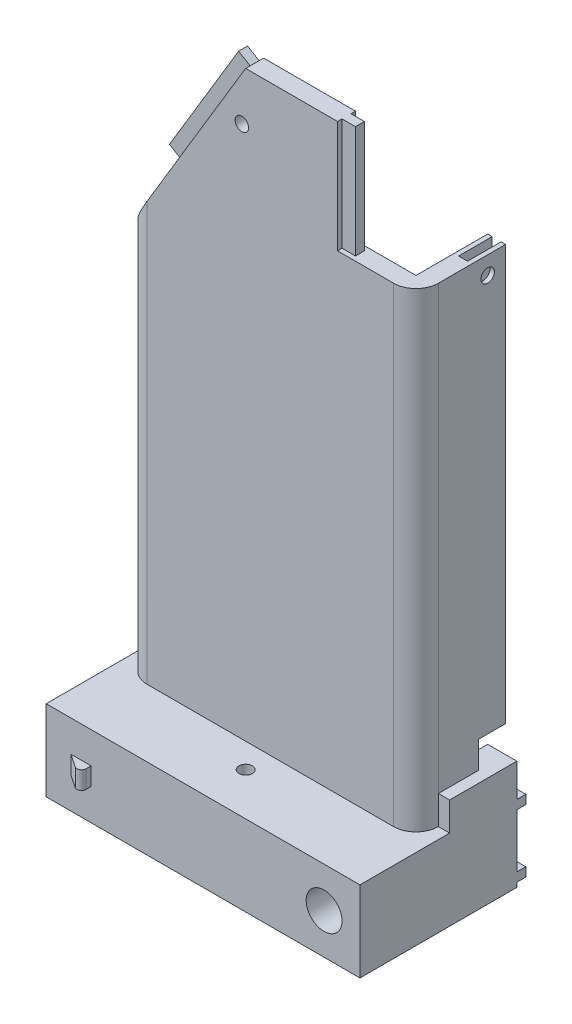
SolidWorks part; units mm, degrees
ref_plane "Front Plane" through (0, 0, 0) normal (0, 0, 1) x (1, 0, 0)
ref_plane "Top Plane" through (0, 0, 0) normal (0, 1, 0) x (1, 0, 0)
ref_plane "Right Plane" through (0, 0, 0) normal (1, 0, 0) x (0, 0, -1)
sketch "Sketch1" plane through (0, 0, 0) normal (0, 1, 0) x (1, 0, 0)
  line L1 (-32.5, -20) -> (32.5, -20)
  line L2 (-32.5, -20) -> (-32.5, 20)
  line L3 (-32.5, 20) -> (32.5, 20)
  line L4 (32.5, -20) -> (32.5, 20)
  line L5 (-32.5, -20) -> (32.5, 20) construction
  line L6 (-32.5, 20) -> (32.5, -20) construction
  point P0 (0, 0)
  dimension "D1" = 65
  dimension "D2" = 40
extrude "Boss-Extrude1" add sketch "Sketch1" along normal blind 130
shell "Shell1" thickness 4 removed face at (0, 0, 0) removed face at (0, 130, 0)
fillet "Fillet1" radius 5 4 edges at (32.5, 65, -20) (32.5, 65, 20) (-32.5, 65, -20) (-32.5, 65, 20)
sketch "Sketch2" plane through (0, 0, 0) normal (0, 0, 1) x (1, 0, 0)
  line L0 (-5.5, 130) -> (-32.5, 85)
  line L1 (28.5, 130) -> (-28.5, 130) construction
  line L2 (-32.5, 130) -> (-32.5, 0) construction
  line L3 (-32.5, 85) -> (-32.5, 130)
  line L4 (-32.5, 130) -> (-5.5, 130)
  dimension "D1" = 5.5
  dimension "D2" = 85
extrude "Cut-Extrude1" cut sketch "Sketch2" against normal through all both and the other way through all
sketch "Sketch3" plane through (0, 0, 0) normal (0, 0, 1) x (1, 0, 0)
  line L1 (32.5, 130) -> (15, 130)
  line L2 (32.5, 130) -> (32.5, 105)
  line L3 (32.5, 105) -> (15, 105)
  line L4 (15, 130) -> (15, 105)
  dimension "D1" = 25
  dimension "D2" = 17.5
extrude "Cut-Extrude2" cut sketch "Sketch3" against normal through all both and the other way through all
sketch "Sketch5" plane through (15, 0, 0) normal (1, 0, 0) x (0, 0, -1)
  line L0 (-18, 130) -> (-18, 105) construction
  line L1 (-16, 130) -> (-20, 130) construction
  line L2 (-16, 105) -> (-20, 105) construction
  line L4 (-19, 130) -> (-17, 130)
  line L5 (-19, 130) -> (-19, 105)
  line L6 (-19, 105) -> (-17, 105)
  line L7 (-17, 130) -> (-17, 105)
  dimension "D1" = 2
extrude "Boss-Extrude2" add sketch "Sketch5" along normal blind 3
mirror "Mirror1" about plane through (0, 0, 0) normal (0, 0, 1) of "Boss-Extrude2"
sketch "Sketch6" plane through (-61.3971, 36.8382, 0) normal (-0.8575, 0.5145, 0) x (0, 0, 1)
  line L0 (-18, 108.6444) -> (-18, 78.6444) construction
  line L1 (-20, 108.6444) -> (-16, 108.6444) construction
  line L3 (-19, 108.6444) -> (-17, 108.6444)
  line L4 (-19, 108.6444) -> (-19, 78.6444)
  line L5 (-19, 78.6444) -> (-17, 78.6444)
  line L6 (-17, 108.6444) -> (-17, 78.6444)
  dimension "D1" = 30
  dimension "D2" = 2
extrude "Boss-Extrude3" add sketch "Sketch6" along normal blind 3
mirror "Mirror2" about plane through (0, 0, 0) normal (0, 0, 1) of "Boss-Extrude3"
sketch "Sketch8" plane through (0, 0, 0) normal (0, 1, 0) x (1, 0, 0)
  line L1 (-35, -35) -> (35, -35)
  line L2 (-35, -35) -> (-35, 35)
  line L3 (-35, 35) -> (35, 35)
  line L4 (35, -35) -> (35, 35)
  line L5 (-35, -35) -> (35, 35) construction
  line L6 (-35, 35) -> (35, -35) construction
  point P0 (0, 0)
  dimension "D1" = 70
  dimension "D2" = 70
extrude "Boss-Extrude4" add sketch "Sketch8" against normal blind 18
sketch "Sketch10" plane through (-35, 0, 0) normal (-1, 0, 0) x (0, 0, 1)
  line L0 (-35, -9) -> (35, -9) construction
  line L1 (-30, -14) -> (30, -14)
  line L2 (-30, -14) -> (-30, -4)
  line L3 (-30, -4) -> (30, -4)
  line L4 (30, -14) -> (30, -4)
  line L5 (-30, -14) -> (30, -4) construction
  line L6 (-30, -4) -> (30, -14) construction
  line L7 (-35, -18) -> (-35, 0) construction
  line L8 (35, -18) -> (35, 0) construction
  line L9 (0, 0) -> (0, -18) construction
  line L10 (-35, -18) -> (35, -18) construction
  point P0 (0, -9)
  dimension "D1" = 60
  dimension "D2" = 10
extrude "Cut-Extrude4" cut sketch "Sketch10" against normal blind 45
sketch "Sketch23" plane through (0, 105, 0) normal (0, 1, 0) x (1, 0, 0)
  line L0 (0, 0) -> (32.5, 0) construction
  line L1 (29.5, 7.5) -> (31.5, 7.5)
  line L2 (29.5, 7.5) -> (29.5, -7.5)
  line L3 (29.5, -7.5) -> (31.5, -7.5)
  line L4 (31.5, 7.5) -> (31.5, -7.5)
  line L5 (32.5, 15) -> (32.5, -15) construction
  line L6 (28.5, 16) -> (28.5, -16) construction
  line L8 (30.5, 14.75) -> (30.5, -14.75) construction
  dimension "D1" = 2
  dimension "D2" = 15
extrude "Cut-Extrude10" cut sketch "Sketch23" against normal blind 10
sketch "Sketch24" plane through (32.5, 0, 0) normal (1, 0, 0) x (0, 0, -1)
  line L1 (15, 105) -> (-15, 105) construction
  circle A0 centre (-4, 101) radius 1.5
  point P2 (0, 105)
  dimension "D3" = 3
  dimension "D1" = 4
  dimension "D2" = 4
extrude "Cut-Extrude11" cut sketch "Sketch24" against normal blind 10 and the other way through all
mirror "Mirror4" about plane through (0, 0, 0) normal (0, 0, 1) of "Cut-Extrude11"
sketch "Sketch27" plane through (0, 0, 0) normal (0, 1, 0) x (1, 0, 0)
  line L0 (35, -35) -> (35, 35) construction
  line L1 (-35, 35) -> (35, 35)
  line L2 (-35, 35) -> (-35, 0)
  line L3 (-35, 0) -> (35, 0)
  line L4 (35, 35) -> (35, 0)
extrude "Cut-Extrude12" cut sketch "Sketch27" against normal through all both and the other way through all
sketch "Sketch29" plane through (0, 0, 0) normal (0, 0, -1) x (-1, 0, 0)
  line L0 (35, -2) -> (-35, -2) construction
  line L1 (35, -4) -> (35, 0) construction
  line L2 (-35, -18) -> (-35, 0) construction
  line L3 (35, -1) -> (-35, -1)
  line L4 (35, -1) -> (35, -3)
  line L5 (35, -3) -> (-35, -3)
  line L6 (-35, -1) -> (-35, -3)
  dimension "D1" = 2
extrude "Boss-Extrude6" add sketch "Sketch29" along normal blind 2
sketch "Sketch30" plane through (0, 0, 0) normal (0, 0, -1) x (-1, 0, 0)
  line L0 (35, -16) -> (-35, -16) construction
  line L1 (35, -18) -> (35, -14) construction
  line L2 (-35, -18) -> (-35, -3) construction
  line L4 (-35, -15) -> (35, -15)
  line L5 (-35, -15) -> (-35, -17)
  line L6 (-35, -17) -> (35, -17)
  line L7 (35, -15) -> (35, -17)
  dimension "D1" = 2
extrude "Boss-Extrude7" add sketch "Sketch30" along normal blind 2
sketch "Sketch31" plane through (0, 0, 35) normal (0, 0, 1) x (1, 0, 0)
  line L0 (35, -18) -> (35, 0) construction
  line L1 (-35, -18) -> (35, -18) construction
  circle A0 centre (27, -9) radius 2
  dimension "D1" = 4
  dimension "D2" = 8
  dimension "D3" = 9
extrude "Cut-Extrude13" cut sketch "Sketch31" against normal through all both and the other way through all
sketch "Sketch32" plane through (0, 0, 35) normal (0, 0, 1) x (1, 0, 0)
  circle A0 centre (27, -9) radius 4
  dimension "D1" = 8
extrude "Cut-Extrude14" cut sketch "Sketch32" against normal blind 15
sketch "Sketch34" plane through (0, 0, 0) normal (0, 1, 0) x (1, 0, 0)
  line L1 (-35, 0) -> (-35, -35) construction
  line L2 (-35, -35) -> (35, -35) construction
  circle A0 centre (0, -25.5) radius 1.5
  dimension "D1" = 3
  dimension "D2" = 9.5
  dimension "D3" = 35
extrude "Cut-Extrude15" cut sketch "Sketch34" against normal through all both and the other way through all
sketch "Sketch35" plane through (0, 0, 0) normal (0, 1, 0) x (1, 0, 0)
  line L1 (-35, 0) -> (35, 0) construction
  line L2 (28.5, -16) -> (28.5, 0) construction
  circle A0 centre (21, -10.5) radius 3
  dimension "D1" = 6
  dimension "D2" = 10.5
  dimension "D3" = 7.5
extrude "Boss-Extrude8" add sketch "Sketch35" along normal blind 7
sketch "Sketch36" plane through (0, 7, 0) normal (0, 1, 0) x (1, 0, 0)
  circle A0 centre (21, -10.5) radius 1.75
  dimension "D1" = 3.5
extrude "Cut-Extrude16" cut sketch "Sketch36" against normal blind 4
pattern_linear "LPattern1" count 2 spacing 43.5 along (-1, 0, 0) of "Boss-Extrude8", "Cut-Extrude16"
sketch "Sketch37" plane through (32.5, 0, 0) normal (1, 0, 0) x (0, 0, -1)
  line L0 (0, 0) -> (0, 105) construction
  line L1 (0, 12.4) -> (-6, 12.4)
  line L2 (0, 12.4) -> (0, 6.4)
  line L3 (0, 6.4) -> (-6, 6.4)
  line L4 (-6, 12.4) -> (-6, 6.4)
  line L5 (-15, 0) -> (0, 0) construction
  dimension "D1" = 6
  dimension "D2" = 6
  dimension "D3" = 6.4
extrude "Cut-Extrude17" cut sketch "Sketch37" against normal through all both and the other way through all
sketch "Sketch38" plane through (32.5, 0, 0) normal (1, 0, 0) x (0, 0, -1)
  line L1 (0, 6.4) -> (-15, 6.4)
  line L2 (0, 6.4) -> (0, 0)
  line L3 (0, 0) -> (-15, 0)
  line L4 (-15, 6.4) -> (-15, 0)
extrude "Boss-Extrude9" add sketch "Sketch38" along normal up to surface (2.5 mm away) up to face at (35, -9, 5.1667)
sketch "Sketch41" plane through (0, -18, 0) normal (0, -1, 0) x (-1, 0, 0)
  circle A0 centre (0, -25.5) radius 4
  dimension "D1" = 8
extrude "Cut-Extrude18" cut sketch "Sketch41" against normal blind 3
sketch "Sketch42" plane through (0, 0, 35) normal (0, 0, 1) x (1, 0, 0)
  line L0 (-35, -9) -> (35, -9) construction
  line L1 (-35, -18) -> (-35, 0) construction
  line L2 (35, -18) -> (35, 0) construction
  line L4 (-29.5, -7) -> (-25, -7)
  line L5 (-29.5, -7) -> (-29.5, -11)
  line L6 (-29.5, -11) -> (-25, -11)
  line L7 (-25, -7) -> (-25, -11)
  dimension "D1" = 4
  dimension "D2" = 4.5
  dimension "D3" = 5.5
extrude "Boss-Extrude10" add sketch "Sketch42" along normal blind 3
sketch "Sketch43" plane through (0, -7, 0) normal (0, 1, 0) x (1, 0, 0)
  line L0 (-25, -38) -> (-29.5, -35)
  line L1 (-29.5, -35) -> (-29.5, -38)
  line L2 (-29.5, -38) -> (-25, -38)
extrude "Cut-Extrude19" cut sketch "Sketch43" against normal through all contours L2 L0 L1
fillet "Fillet2" radius 1 1 edges at (-25, -9, 38)
sketch "Sketch46" plane through (0, 0, 20) normal (0, 0, 1) x (1, 0, 0)
  line L0 (-27.5, 93.3333) -> (-5.5, 130) construction
  line L1 (-6.3575, 118.8526) -> (-10.645, 121.4251) construction
  line L2 (-5.5, 130) -> (-20.9349, 104.2752) construction
  circle A0 centre (-6.3575, 118.8526) radius 1.5
  dimension "D1" = 5
  dimension "D2" = 3
  dimension "D3" = 10
  dimension "D4" = 5
extrude "Cut-Extrude20" cut sketch "Sketch46" against normal blind 10
